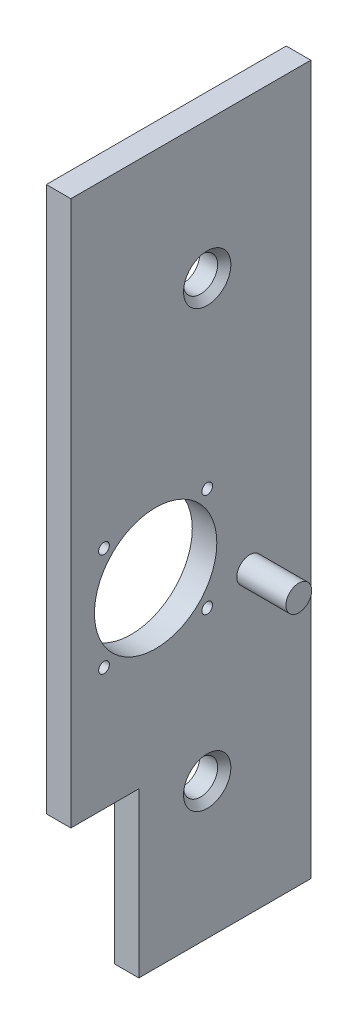
SolidWorks part; units mm, degrees
material "6061-T6 (SS)"
ref_plane "Front Plane" through (0, 0, 0) normal (1, 0, 0) x (0, 1, 0)
ref_plane "Top Plane" through (0, 0, 0) normal (0, 0, 1) x (0, 1, 0)
ref_plane "Right Plane" through (0, 0, 0) normal (0, 1, 0) x (-1, 0, 0)
sketch "Sketch1" plane through (0, 0, 0) normal (1, 0, 0) x (0, 1, 0)
  line L1 (0, 0) -> (-165.1, 0)
  line L2 (0, 0) -> (0, 55.88)
  line L3 (0, 55.88) -> (-165.1, 55.88)
  line L4 (-165.1, 0) -> (-165.1, 55.88)
  line L12 (-74.378, 24.1168) -> (-98.4197, 24.1168) construction
  line L13 (-74.378, 24.1168) -> (-74.378, 48.1585) construction
  line L14 (-74.378, 48.1585) -> (-98.4197, 48.1585) construction
  line L15 (-98.4197, 24.1168) -> (-98.4197, 48.1585) construction
  line L16 (-74.378, 24.1168) -> (-98.4197, 48.1585) construction
  line L17 (-74.378, 48.1585) -> (-98.4197, 24.1168) construction
  line L21 (-165.1, 55.88) -> (-155.6671, 55.88) construction
  line L22 (-165.1, 55.88) -> (-165.1, 46.99) construction
  line L26 (-165.1, 55.88) -> (-126.9378, 55.88)
  line L27 (-165.1, 55.88) -> (-165.1, 40.0526)
  line L28 (-165.1, 40.0526) -> (-126.9378, 40.0526)
  line L29 (-126.9378, 55.88) -> (-126.9378, 40.0526)
  circle A0 centre (-133.35, 24.13) radius 3.9751
  circle A1 centre (-31.9024, 24.13) radius 3.9751
  circle A4 centre (-86.3988, 36.1377) radius 14.25
  circle A6 centre (-31.9024, 24.13) radius 27.305 construction
  circle A7 centre (-133.35, 24.13) radius 27.305 construction
  circle A8 centre (-95.639, 14.224) radius 3.175 construction
  dimension "D1" = 7.9502
  dimension "D5" = 28.5
  dimension "D13" = 54.61
  dimension "D14" = 54.61
  dimension "D3" = 6.35
  dimension "D6" = 55.88
  dimension "D9" = 24.13
  dimension "D10" = 31.75
  dimension "D11" = 31.9024
  dimension "D12" = 165.1
  dimension "D4" = 34
  dimension "D2" = 14.224
extrude "Boss-Extrude1" add sketch "Sketch1" along normal blind 5.715 contours L3 L29 L28 L4 L1 L2 A4 A1 A0 region at (0, -82.55, 1.743)
sketch "Sketch7" plane through (5.715, 0, 0) normal (1, 0, 0) x (0, 1, 0)
  circle A0 centre (-95.639, 14.224) radius 3
  dimension "D1" = 6
extrude "Boss-Extrude2" add sketch "Sketch7" along normal blind 11.43
hole_wizard "M3x0.5 Tapped Hole1" positions "Sketch5" profile "Sketch6" tap size "M3x0.5" standard "ANSI Metric" end condition up to next
sketch "Sketch5" plane through (5.715, 0, 0) normal (1, 0, 0) x (0, 0, -1)
  point P0 (-48.1585, -74.378)
  point P3 (-24.1168, -74.378)
  point P6 (-24.1168, -98.4197)
  point P9 (-48.1585, -98.4197)
sketch "Sketch6" plane through (5.715, -74.378, 48.1585) normal (0, 1, 0) x (0, 0, -1)
  line L0 (0, 0) -> (0, 5.715)
  line L1 (0, 5.715) -> (1.25, 5.715)
  line L2 (1.25, 5.715) -> (1.25, 0)
  line L5 (1.25, 0) -> (0, 0)
  line L11 (0, -6.35) -> (0, 107.95) construction
  dimension "Thru Tap Drill Dia." = 2.5
  dimension "Thru Tap Drill Depth" = 5.715
cosmetic thread "Hole Thread5" parameters "D2"=3
cosmetic thread "Hole Thread6" parameters "D2"=3
cosmetic thread "Hole Thread7" parameters "D2"=3
cosmetic thread "Hole Thread8" parameters "D2"=3
ref_plane "Plane1" through (12.7, 0, 0) normal (1, 0, 0) x (0, 1, 0)
sketch "Pully" plane through (12.7, 0, 0) normal (1, 0, 0) x (0, 1, 0)
  line L1 (-132.9499, 45.1262) -> (-86.2445, 44.2362)
  line L2 (-133.35, 3.13) -> (-31.9024, 3.13)
  line L3 (-43.622, 41.5556) -> (-92.0952, 8.9548)
  line L4 (-98.7871, 19.7387) -> (-82.3831, 29.1032)
  line L5 (-132.9499, 45.1262) -> (-133.35, 24.13) construction
  line L6 (-133.35, 24.13) -> (-133.35, 3.13) construction
  line L7 (-86.2445, 44.2362) -> (-86.3988, 36.1377) construction
  line L8 (-86.3988, 36.1377) -> (-82.3831, 29.1032) construction
  line L9 (-43.622, 41.5556) -> (-31.9024, 24.13) construction
  line L10 (-31.9024, 24.13) -> (-31.9024, 3.13) construction
  line L11 (-98.7871, 19.7387) -> (-95.639, 14.224) construction
  line L12 (-95.639, 14.224) -> (-92.0952, 8.9548) construction
  circle A0 centre (-133.35, 24.13) radius 21
  circle A1 centre (-95.639, 14.224) radius 6.35
  circle A2 centre (-86.3988, 36.1377) radius 8.1
  circle A3 centre (-31.9024, 24.13) radius 21
  dimension "D2" = 12.7
  dimension "D3" = 16.2
  dimension "D1" = 42
  dimension "D4" = 181.092
  dimension "D5" = 213.923
  dimension "D6" = 149.188
  dimension "D7" = 184.202
chamfer "Chamfer1" distance 1.5367 angle 45 2 edges at (5.715, -31.9024, 20.1549) (5.715, -133.35, 20.1549)
equation "\"D1@Pully\"=42mm"
equation "\"D3@Pully\"=16.2mm"
equation "\"D4@Sketch1\"=34mm"
equation "\"D5@Sketch1\"=28.5mm"
equation "\"D1@Sketch7\"=6mm"
